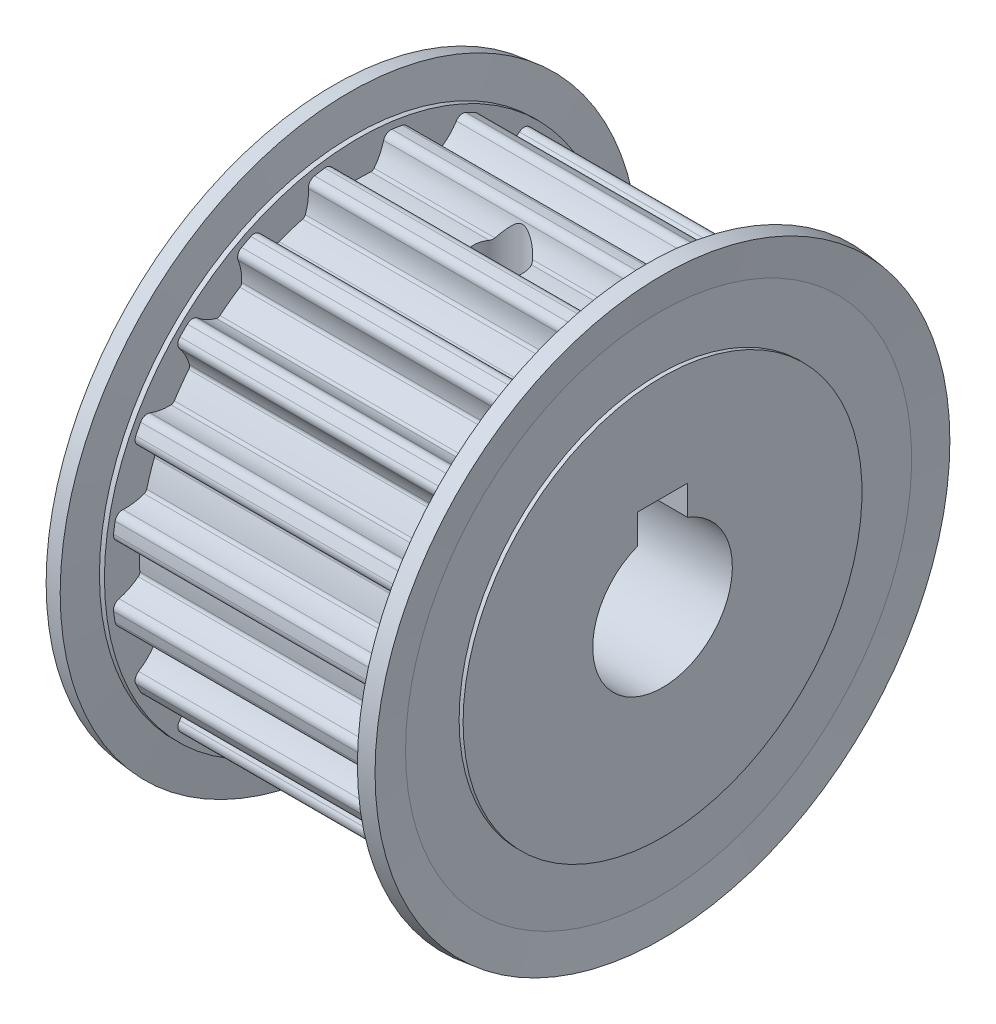
SolidWorks part; units mm, degrees
ref_plane "前视基准面" through (0, 0, 0) normal (0, 0, 1) x (1, 0, 0)
ref_plane "上视基准面" through (0, 0, 0) normal (0, 1, 0) x (1, 0, 0)
ref_plane "右视基准面" through (0, 0, 0) normal (1, 0, 0) x (0, 0, -1)
sketch "草图1" plane through (0, 0, 0) normal (0, 0, 1) x (1, 0, 0)
  line L0 (0, 20) -> (0, 7)
  line L1 (0, 7) -> (48, 7)
  line L2 (48, 7) -> (48, 10.5)
  line L3 (48, 10.5) -> (33, 10.5)
  line L4 (33, 10.5) -> (33, 20)
  line L5 (33, 20) -> (32.6, 20)
  line L6 (32.6, 20) -> (32.6, 25.3748)
  line L7 (32.6, 25.3748) -> (32.9899, 28.8201)
  line L8 (32.9899, 28.8201) -> (31.4, 29)
  line L9 (31.4, 29) -> (31, 25.465)
  line L10 (31, 25.465) -> (30.5, 25.465)
  line L11 (30.5, 25.465) -> (30.5, 24.78)
  line L12 (30.5, 24.78) -> (2.5, 24.78)
  line L13 (2.5, 24.78) -> (2.5, 25.465)
  line L14 (2.5, 25.465) -> (2, 25.465)
  line L15 (2, 25.465) -> (1.6, 29)
  line L16 (1.6, 29) -> (0.0101, 28.8201)
  line L17 (0.0101, 28.8201) -> (0.4, 25.3748)
  line L18 (0.4, 25.3748) -> (0.4, 20)
  line L19 (0.4, 20) -> (0, 20)
  line L20 (48, 0) -> (0, 0) construction
  dimension "D1" = 7
  dimension "D2" = 9.5
revolve "旋转1" add sketch "草图1" angle 360 about L20 reverse direction yes
sketch "草图2" plane through (0, 0, 0) normal (0, 0, 1) x (1, 0, 0)
  line L0 (33, 0) -> (33, 29)
  line L1 (33, 29) -> (66, 29)
  line L2 (66, 29) -> (66, 0)
  line L3 (66, 0) -> (33, 0)
  line L4 (66, 0) -> (33, 0) construction
revolve "切除-旋转1" cut sketch "草图2" angle 360 about L4 reverse direction yes
ref_plane "基准面4" through (2.5, 0, 0) normal (1, 0, 0) x (0, 0, -1)
sketch "草图3" plane through (2.5, 0, 0) normal (1, 0, 0) x (0, 0, -1)
  line L0 (3.3567, 24.5516) -> (3.3567, 33.04)
  line L1 (3.3567, 33.04) -> (-3.3567, 33.04)
  line L2 (-3.3567, 33.04) -> (-3.3567, 24.5516)
  arc A0 (-3.3567, 24.5516) -> (-2.5292, 23.9974) centre (-3.2551, 23.8085) cw
  arc A1 (-2.5292, 23.9974) -> (-1.5758, 22.0681) centre (2.6, 25.3319) ccw
  arc A2 (-1.5758, 22.0681) -> (-1.2381, 21.9151) centre (-1.2607, 22.3144) ccw
  arc A3 (-1.2381, 21.9151) -> (1.2381, 21.9151) centre (0, 0) cw
  arc A4 (1.2381, 21.9151) -> (1.5758, 22.0681) centre (1.2607, 22.3144) ccw
  arc A5 (1.5758, 22.0681) -> (2.5292, 23.9974) centre (-2.6, 25.3319) ccw
  arc A6 (2.5292, 23.9974) -> (3.3567, 24.5516) centre (3.2551, 23.8085) cw
extrude "切除-拉伸1" cut sketch "草图3" along normal blind 28
sketch "草图5" plane through (2.5, 0, 0) normal (1, 0, 0) x (0, 0, -1)
  line L0 (-4.3945, 24.3872) -> (-7.0176, 32.4602)
  line L1 (-7.0176, 32.4602) -> (-13.4023, 30.3856)
  line L2 (-13.4023, 30.3856) -> (-10.7792, 22.3127)
  arc A0 (-10.7792, 22.3127) -> (-9.821, 22.0413) centre (-10.453, 21.6374) cw
  arc A1 (-9.821, 22.0413) -> (-8.3181, 20.501) centre (-5.3552, 24.8955) ccw
  arc A2 (-8.3181, 20.501) -> (-7.9496, 20.4599) centre (-8.0945, 20.8327) ccw
  arc A3 (-7.9496, 20.4599) -> (-5.5946, 21.225) centre (0, 0) cw
  arc A4 (-5.5946, 21.225) -> (-5.3207, 21.475) centre (-5.6966, 21.6118) ccw
  arc A5 (-5.3207, 21.475) -> (-5.0102, 23.6044) centre (-10.3007, 23.2886) ccw
  arc A6 (-5.0102, 23.6044) -> (-4.3945, 24.3872) centre (-4.2615, 23.6491) cw
sketch "草图6" plane through (2.5, 0, 0) normal (1, 0, 0) x (0, 0, -1)
  line L0 (-11.7155, 21.8357) -> (-16.7048, 28.7029)
  line L1 (-16.7048, 28.7029) -> (-22.136, 24.7569)
  line L2 (-22.136, 24.7569) -> (-17.1467, 17.8897)
  arc A0 (-17.1467, 17.8897) -> (-16.1515, 17.9276) centre (-16.6277, 17.3482) cw
  arc A1 (-16.1515, 17.9276) -> (-14.2462, 16.9272) centre (-12.7863, 22.0222) ccw
  arc A2 (-14.2462, 16.9272) -> (-13.883, 17.0019) centre (-14.136, 17.3117) ccw
  arc A3 (-13.883, 17.0019) -> (-11.8797, 18.4574) centre (0, 0) cw
  arc A4 (-11.8797, 18.4574) -> (-11.6964, 18.7797) centre (-12.0962, 18.7937) ccw
  arc A5 (-11.6964, 18.7797) -> (-12.0591, 20.9009) centre (-16.9932, 18.9657) ccw
  arc A6 (-12.0591, 20.9009) -> (-11.7155, 21.8357) centre (-11.3609, 21.1748) cw
sketch "草图7" plane through (2.5, 0, 0) normal (1, 0, 0) x (0, 0, -1)
  line L0 (-17.8897, 17.1467) -> (-24.7569, 22.136)
  line L1 (-24.7569, 22.136) -> (-28.7029, 16.7048)
  line L2 (-28.7029, 16.7048) -> (-21.8357, 11.7155)
  arc A0 (-21.8357, 11.7155) -> (-20.9009, 12.0591) centre (-21.1748, 11.3609) cw
  arc A1 (-20.9009, 12.0591) -> (-18.7797, 11.6964) centre (-18.9657, 16.9932) ccw
  arc A2 (-18.7797, 11.6964) -> (-18.4574, 11.8797) centre (-18.7937, 12.0962) ccw
  arc A3 (-18.4574, 11.8797) -> (-17.0019, 13.883) centre (0, 0) cw
  arc A4 (-17.0019, 13.883) -> (-16.9272, 14.2462) centre (-17.3117, 14.136) ccw
  arc A5 (-16.9272, 14.2462) -> (-17.9276, 16.1515) centre (-22.0222, 12.7863) ccw
  arc A6 (-17.9276, 16.1515) -> (-17.8897, 17.1467) centre (-17.3482, 16.6277) cw
sketch "草图8" plane through (2.5, 0, 0) normal (1, 0, 0) x (0, 0, -1)
  line L0 (-22.3127, 10.7792) -> (-30.3856, 13.4023)
  line L1 (-30.3856, 13.4023) -> (-32.4602, 7.0176)
  line L2 (-32.4602, 7.0176) -> (-24.3872, 4.3945)
  arc A0 (-24.3872, 4.3945) -> (-23.6044, 5.0102) centre (-23.6491, 4.2615) cw
  arc A1 (-23.6044, 5.0102) -> (-21.475, 5.3207) centre (-23.2886, 10.3007) ccw
  arc A2 (-21.475, 5.3207) -> (-21.225, 5.5946) centre (-21.6118, 5.6966) ccw
  arc A3 (-21.225, 5.5946) -> (-20.4599, 7.9496) centre (0, 0) cw
  arc A4 (-20.4599, 7.9496) -> (-20.501, 8.3181) centre (-20.8327, 8.0945) ccw
  arc A5 (-20.501, 8.3181) -> (-22.0413, 9.821) centre (-24.8955, 5.3552) ccw
  arc A6 (-22.0413, 9.821) -> (-22.3127, 10.7792) centre (-21.6374, 10.453) cw
sketch "草图9" plane through (2.5, 0, 0) normal (1, 0, 0) x (0, 0, -1)
  line L0 (-24.5516, 3.3567) -> (-33.04, 3.3567)
  line L1 (-33.04, 3.3567) -> (-33.04, -3.3567)
  line L2 (-33.04, -3.3567) -> (-24.5516, -3.3567)
  arc A0 (-24.5516, -3.3567) -> (-23.9974, -2.5292) centre (-23.8085, -3.2551) cw
  arc A1 (-23.9974, -2.5292) -> (-22.0681, -1.5758) centre (-25.3319, 2.6) ccw
  arc A2 (-22.0681, -1.5758) -> (-21.9151, -1.2381) centre (-22.3144, -1.2607) ccw
  arc A3 (-21.9151, -1.2381) -> (-21.9151, 1.2381) centre (0, 0) cw
  arc A4 (-21.9151, 1.2381) -> (-22.0681, 1.5758) centre (-22.3144, 1.2607) ccw
  arc A5 (-22.0681, 1.5758) -> (-23.9974, 2.5292) centre (-25.3319, -2.6) ccw
  arc A6 (-23.9974, 2.5292) -> (-24.5516, 3.3567) centre (-23.8085, 3.2551) cw
sketch "草图10" plane through (2.5, 0, 0) normal (1, 0, 0) x (0, 0, -1)
  line L0 (-24.3872, -4.3945) -> (-32.4602, -7.0176)
  line L1 (-32.4602, -7.0176) -> (-30.3856, -13.4023)
  line L2 (-30.3856, -13.4023) -> (-22.3127, -10.7792)
  arc A0 (-22.3127, -10.7792) -> (-22.0413, -9.821) centre (-21.6374, -10.453) cw
  arc A1 (-22.0413, -9.821) -> (-20.501, -8.3181) centre (-24.8955, -5.3552) ccw
  arc A2 (-20.501, -8.3181) -> (-20.4599, -7.9496) centre (-20.8327, -8.0945) ccw
  arc A3 (-20.4599, -7.9496) -> (-21.225, -5.5946) centre (0, 0) cw
  arc A4 (-21.225, -5.5946) -> (-21.475, -5.3207) centre (-21.6118, -5.6966) ccw
  arc A5 (-21.475, -5.3207) -> (-23.6044, -5.0102) centre (-23.2886, -10.3007) ccw
  arc A6 (-23.6044, -5.0102) -> (-24.3872, -4.3945) centre (-23.6491, -4.2615) cw
sketch "草图11" plane through (2.5, 0, 0) normal (1, 0, 0) x (0, 0, -1)
  line L0 (-21.8357, -11.7155) -> (-28.7029, -16.7048)
  line L1 (-28.7029, -16.7048) -> (-24.7569, -22.136)
  line L2 (-24.7569, -22.136) -> (-17.8897, -17.1467)
  arc A0 (-17.8897, -17.1467) -> (-17.9276, -16.1515) centre (-17.3482, -16.6277) cw
  arc A1 (-17.9276, -16.1515) -> (-16.9272, -14.2462) centre (-22.0222, -12.7863) ccw
  arc A2 (-16.9272, -14.2462) -> (-17.0019, -13.883) centre (-17.3117, -14.136) ccw
  arc A3 (-17.0019, -13.883) -> (-18.4574, -11.8797) centre (0, 0) cw
  arc A4 (-18.4574, -11.8797) -> (-18.7797, -11.6964) centre (-18.7937, -12.0962) ccw
  arc A5 (-18.7797, -11.6964) -> (-20.9009, -12.0591) centre (-18.9657, -16.9932) ccw
  arc A6 (-20.9009, -12.0591) -> (-21.8357, -11.7155) centre (-21.1748, -11.3609) cw
sketch "草图12" plane through (2.5, 0, 0) normal (1, 0, 0) x (0, 0, -1)
  line L0 (-17.1467, -17.8897) -> (-22.136, -24.7569)
  line L1 (-22.136, -24.7569) -> (-16.7048, -28.7029)
  line L2 (-16.7048, -28.7029) -> (-11.7155, -21.8357)
  arc A0 (-11.7155, -21.8357) -> (-12.0591, -20.9009) centre (-11.3609, -21.1748) cw
  arc A1 (-12.0591, -20.9009) -> (-11.6964, -18.7797) centre (-16.9932, -18.9657) ccw
  arc A2 (-11.6964, -18.7797) -> (-11.8797, -18.4574) centre (-12.0962, -18.7937) ccw
  arc A3 (-11.8797, -18.4574) -> (-13.883, -17.0019) centre (0, 0) cw
  arc A4 (-13.883, -17.0019) -> (-14.2462, -16.9272) centre (-14.136, -17.3117) ccw
  arc A5 (-14.2462, -16.9272) -> (-16.1515, -17.9276) centre (-12.7863, -22.0222) ccw
  arc A6 (-16.1515, -17.9276) -> (-17.1467, -17.8897) centre (-16.6277, -17.3482) cw
sketch "草图13" plane through (2.5, 0, 0) normal (1, 0, 0) x (0, 0, -1)
  line L0 (-10.7792, -22.3127) -> (-13.4023, -30.3856)
  line L1 (-13.4023, -30.3856) -> (-7.0176, -32.4602)
  line L2 (-7.0176, -32.4602) -> (-4.3945, -24.3872)
  arc A0 (-4.3945, -24.3872) -> (-5.0102, -23.6044) centre (-4.2615, -23.6491) cw
  arc A1 (-5.0102, -23.6044) -> (-5.3207, -21.475) centre (-10.3007, -23.2886) ccw
  arc A2 (-5.3207, -21.475) -> (-5.5946, -21.225) centre (-5.6966, -21.6118) ccw
  arc A3 (-5.5946, -21.225) -> (-7.9496, -20.4599) centre (0, 0) cw
  arc A4 (-7.9496, -20.4599) -> (-8.3181, -20.501) centre (-8.0945, -20.8327) ccw
  arc A5 (-8.3181, -20.501) -> (-9.821, -22.0413) centre (-5.3552, -24.8955) ccw
  arc A6 (-9.821, -22.0413) -> (-10.7792, -22.3127) centre (-10.453, -21.6374) cw
sketch "草图14" plane through (2.5, 0, 0) normal (1, 0, 0) x (0, 0, -1)
  line L0 (-3.3567, -24.5516) -> (-3.3567, -33.04)
  line L1 (-3.3567, -33.04) -> (3.3567, -33.04)
  line L2 (3.3567, -33.04) -> (3.3567, -24.5516)
  arc A0 (3.3567, -24.5516) -> (2.5292, -23.9974) centre (3.2551, -23.8085) cw
  arc A1 (2.5292, -23.9974) -> (1.5758, -22.0681) centre (-2.6, -25.3319) ccw
  arc A2 (1.5758, -22.0681) -> (1.2381, -21.9151) centre (1.2607, -22.3144) ccw
  arc A3 (1.2381, -21.9151) -> (-1.2381, -21.9151) centre (0, 0) cw
  arc A4 (-1.2381, -21.9151) -> (-1.5758, -22.0681) centre (-1.2607, -22.3144) ccw
  arc A5 (-1.5758, -22.0681) -> (-2.5292, -23.9974) centre (2.6, -25.3319) ccw
  arc A6 (-2.5292, -23.9974) -> (-3.3567, -24.5516) centre (-3.2551, -23.8085) cw
sketch "草图15" plane through (2.5, 0, 0) normal (1, 0, 0) x (0, 0, -1)
  line L0 (4.3945, -24.3872) -> (7.0176, -32.4602)
  line L1 (7.0176, -32.4602) -> (13.4023, -30.3856)
  line L2 (13.4023, -30.3856) -> (10.7792, -22.3127)
  arc A0 (10.7792, -22.3127) -> (9.821, -22.0413) centre (10.453, -21.6374) cw
  arc A1 (9.821, -22.0413) -> (8.3181, -20.501) centre (5.3552, -24.8955) ccw
  arc A2 (8.3181, -20.501) -> (7.9496, -20.4599) centre (8.0945, -20.8327) ccw
  arc A3 (7.9496, -20.4599) -> (5.5946, -21.225) centre (0, 0) cw
  arc A4 (5.5946, -21.225) -> (5.3207, -21.475) centre (5.6966, -21.6118) ccw
  arc A5 (5.3207, -21.475) -> (5.0102, -23.6044) centre (10.3007, -23.2886) ccw
  arc A6 (5.0102, -23.6044) -> (4.3945, -24.3872) centre (4.2615, -23.6491) cw
sketch "草图16" plane through (2.5, 0, 0) normal (1, 0, 0) x (0, 0, -1)
  line L0 (11.7155, -21.8357) -> (16.7048, -28.7029)
  line L1 (16.7048, -28.7029) -> (22.136, -24.7569)
  line L2 (22.136, -24.7569) -> (17.1467, -17.8897)
  arc A0 (17.1467, -17.8897) -> (16.1515, -17.9276) centre (16.6277, -17.3482) cw
  arc A1 (16.1515, -17.9276) -> (14.2462, -16.9272) centre (12.7863, -22.0222) ccw
  arc A2 (14.2462, -16.9272) -> (13.883, -17.0019) centre (14.136, -17.3117) ccw
  arc A3 (13.883, -17.0019) -> (11.8797, -18.4574) centre (0, 0) cw
  arc A4 (11.8797, -18.4574) -> (11.6964, -18.7797) centre (12.0962, -18.7937) ccw
  arc A5 (11.6964, -18.7797) -> (12.0591, -20.9009) centre (16.9932, -18.9657) ccw
  arc A6 (12.0591, -20.9009) -> (11.7155, -21.8357) centre (11.3609, -21.1748) cw
sketch "草图17" plane through (2.5, 0, 0) normal (1, 0, 0) x (0, 0, -1)
  line L0 (17.8897, -17.1467) -> (24.7569, -22.136)
  line L1 (24.7569, -22.136) -> (28.7029, -16.7048)
  line L2 (28.7029, -16.7048) -> (21.8357, -11.7155)
  arc A0 (21.8357, -11.7155) -> (20.9009, -12.0591) centre (21.1748, -11.3609) cw
  arc A1 (20.9009, -12.0591) -> (18.7797, -11.6964) centre (18.9657, -16.9932) ccw
  arc A2 (18.7797, -11.6964) -> (18.4574, -11.8797) centre (18.7937, -12.0962) ccw
  arc A3 (18.4574, -11.8797) -> (17.0019, -13.883) centre (0, 0) cw
  arc A4 (17.0019, -13.883) -> (16.9272, -14.2462) centre (17.3117, -14.136) ccw
  arc A5 (16.9272, -14.2462) -> (17.9276, -16.1515) centre (22.0222, -12.7863) ccw
  arc A6 (17.9276, -16.1515) -> (17.8897, -17.1467) centre (17.3482, -16.6277) cw
sketch "草图18" plane through (2.5, 0, 0) normal (1, 0, 0) x (0, 0, -1)
  line L0 (22.3127, -10.7792) -> (30.3856, -13.4023)
  line L1 (30.3856, -13.4023) -> (32.4602, -7.0176)
  line L2 (32.4602, -7.0176) -> (24.3872, -4.3945)
  arc A0 (24.3872, -4.3945) -> (23.6044, -5.0102) centre (23.6491, -4.2615) cw
  arc A1 (23.6044, -5.0102) -> (21.475, -5.3207) centre (23.2886, -10.3007) ccw
  arc A2 (21.475, -5.3207) -> (21.225, -5.5946) centre (21.6118, -5.6966) ccw
  arc A3 (21.225, -5.5946) -> (20.4599, -7.9496) centre (0, 0) cw
  arc A4 (20.4599, -7.9496) -> (20.501, -8.3181) centre (20.8327, -8.0945) ccw
  arc A5 (20.501, -8.3181) -> (22.0413, -9.821) centre (24.8955, -5.3552) ccw
  arc A6 (22.0413, -9.821) -> (22.3127, -10.7792) centre (21.6374, -10.453) cw
sketch "草图19" plane through (2.5, 0, 0) normal (1, 0, 0) x (0, 0, -1)
  line L0 (24.5516, -3.3567) -> (33.04, -3.3567)
  line L1 (33.04, -3.3567) -> (33.04, 3.3567)
  line L2 (33.04, 3.3567) -> (24.5516, 3.3567)
  arc A0 (24.5516, 3.3567) -> (23.9974, 2.5292) centre (23.8085, 3.2551) cw
  arc A1 (23.9974, 2.5292) -> (22.0681, 1.5758) centre (25.3319, -2.6) ccw
  arc A2 (22.0681, 1.5758) -> (21.9151, 1.2381) centre (22.3144, 1.2607) ccw
  arc A3 (21.9151, 1.2381) -> (21.9151, -1.2381) centre (0, 0) cw
  arc A4 (21.9151, -1.2381) -> (22.0681, -1.5758) centre (22.3144, -1.2607) ccw
  arc A5 (22.0681, -1.5758) -> (23.9974, -2.5292) centre (25.3319, 2.6) ccw
  arc A6 (23.9974, -2.5292) -> (24.5516, -3.3567) centre (23.8085, -3.2551) cw
sketch "草图20" plane through (2.5, 0, 0) normal (1, 0, 0) x (0, 0, -1)
  line L0 (24.3872, 4.3945) -> (32.4602, 7.0176)
  line L1 (32.4602, 7.0176) -> (30.3856, 13.4023)
  line L2 (30.3856, 13.4023) -> (22.3127, 10.7792)
  arc A0 (22.3127, 10.7792) -> (22.0413, 9.821) centre (21.6374, 10.453) cw
  arc A1 (22.0413, 9.821) -> (20.501, 8.3181) centre (24.8955, 5.3552) ccw
  arc A2 (20.501, 8.3181) -> (20.4599, 7.9496) centre (20.8327, 8.0945) ccw
  arc A3 (20.4599, 7.9496) -> (21.225, 5.5946) centre (0, 0) cw
  arc A4 (21.225, 5.5946) -> (21.475, 5.3207) centre (21.6118, 5.6966) ccw
  arc A5 (21.475, 5.3207) -> (23.6044, 5.0102) centre (23.2886, 10.3007) ccw
  arc A6 (23.6044, 5.0102) -> (24.3872, 4.3945) centre (23.6491, 4.2615) cw
sketch "草图21" plane through (2.5, 0, 0) normal (1, 0, 0) x (0, 0, -1)
  line L0 (21.8357, 11.7155) -> (28.7029, 16.7048)
  line L1 (28.7029, 16.7048) -> (24.7569, 22.136)
  line L2 (24.7569, 22.136) -> (17.8897, 17.1467)
  arc A0 (17.8897, 17.1467) -> (17.9276, 16.1515) centre (17.3482, 16.6277) cw
  arc A1 (17.9276, 16.1515) -> (16.9272, 14.2462) centre (22.0222, 12.7863) ccw
  arc A2 (16.9272, 14.2462) -> (17.0019, 13.883) centre (17.3117, 14.136) ccw
  arc A3 (17.0019, 13.883) -> (18.4574, 11.8797) centre (0, 0) cw
  arc A4 (18.4574, 11.8797) -> (18.7797, 11.6964) centre (18.7937, 12.0962) ccw
  arc A5 (18.7797, 11.6964) -> (20.9009, 12.0591) centre (18.9657, 16.9932) ccw
  arc A6 (20.9009, 12.0591) -> (21.8357, 11.7155) centre (21.1748, 11.3609) cw
sketch "草图22" plane through (2.5, 0, 0) normal (1, 0, 0) x (0, 0, -1)
  line L0 (17.1467, 17.8897) -> (22.136, 24.7569)
  line L1 (22.136, 24.7569) -> (16.7048, 28.7029)
  line L2 (16.7048, 28.7029) -> (11.7155, 21.8357)
  arc A0 (11.7155, 21.8357) -> (12.0591, 20.9009) centre (11.3609, 21.1748) cw
  arc A1 (12.0591, 20.9009) -> (11.6964, 18.7797) centre (16.9932, 18.9657) ccw
  arc A2 (11.6964, 18.7797) -> (11.8797, 18.4574) centre (12.0962, 18.7937) ccw
  arc A3 (11.8797, 18.4574) -> (13.883, 17.0019) centre (0, 0) cw
  arc A4 (13.883, 17.0019) -> (14.2462, 16.9272) centre (14.136, 17.3117) ccw
  arc A5 (14.2462, 16.9272) -> (16.1515, 17.9276) centre (12.7863, 22.0222) ccw
  arc A6 (16.1515, 17.9276) -> (17.1467, 17.8897) centre (16.6277, 17.3482) cw
sketch "草图23" plane through (2.5, 0, 0) normal (1, 0, 0) x (0, 0, -1)
  line L0 (10.7792, 22.3127) -> (13.4023, 30.3856)
  line L1 (13.4023, 30.3856) -> (7.0176, 32.4602)
  line L2 (7.0176, 32.4602) -> (4.3945, 24.3872)
  arc A0 (4.3945, 24.3872) -> (5.0102, 23.6044) centre (4.2615, 23.6491) cw
  arc A1 (5.0102, 23.6044) -> (5.3207, 21.475) centre (10.3007, 23.2886) ccw
  arc A2 (5.3207, 21.475) -> (5.5946, 21.225) centre (5.6966, 21.6118) ccw
  arc A3 (5.5946, 21.225) -> (7.9496, 20.4599) centre (0, 0) cw
  arc A4 (7.9496, 20.4599) -> (8.3181, 20.501) centre (8.0945, 20.8327) ccw
  arc A5 (8.3181, 20.501) -> (9.821, 22.0413) centre (5.3552, 24.8955) ccw
  arc A6 (9.821, 22.0413) -> (10.7792, 22.3127) centre (10.453, 21.6374) cw
extrude "切除-拉伸2" cut sketch "草图5" along normal blind 28
extrude "切除-拉伸3" cut sketch "草图6" along normal blind 28
extrude "切除-拉伸4" cut sketch "草图7" along normal blind 28
extrude "切除-拉伸5" cut sketch "草图8" along normal blind 28
extrude "切除-拉伸6" cut sketch "草图9" along normal blind 28
extrude "切除-拉伸7" cut sketch "草图10" along normal blind 28
extrude "切除-拉伸8" cut sketch "草图11" along normal blind 28
extrude "切除-拉伸9" cut sketch "草图12" along normal blind 28
extrude "切除-拉伸10" cut sketch "草图13" along normal blind 28
extrude "切除-拉伸11" cut sketch "草图14" along normal blind 28
extrude "切除-拉伸12" cut sketch "草图15" along normal blind 28
extrude "切除-拉伸13" cut sketch "草图16" along normal blind 28
extrude "切除-拉伸14" cut sketch "草图17" along normal blind 28
extrude "切除-拉伸15" cut sketch "草图18" along normal blind 28
extrude "切除-拉伸16" cut sketch "草图19" along normal blind 28
extrude "切除-拉伸17" cut sketch "草图20" along normal blind 28
extrude "切除-拉伸18" cut sketch "草图21" along normal blind 28
extrude "切除-拉伸19" cut sketch "草图22" along normal blind 28
extrude "切除-拉伸20" cut sketch "草图23" along normal blind 28
ref_plane "基准面5" through (16.5, 0, 0) normal (1, 0, 0) x (0, 0, -1)
sketch "草图24" plane through (16.5, 0, 0) normal (1, 0, 0) x (0, 0, -1)
  line L0 (0, 24.78) -> (2.4585, 24.78)
  line L1 (2.4585, 24.78) -> (2.4585, 0)
  line L2 (2.4585, 0) -> (0, 0)
  line L3 (0, 0) -> (0, 24.78)
  line L4 (0, 12.3) -> (0, 24.78) construction
revolve "切除-旋转2" cut sketch "草图24" angle 360 about L4 reverse direction yes
cosmetic thread "装饰螺纹线1" parameters "D1"=26.0658, "D2"=6
sketch "草图25" plane through (16.5, 0, 0) normal (1, 0, 0) x (0, 0, -1)
  line L0 (21.4601, -12.39) -> (20.2309, -14.5191)
  line L1 (20.2309, -14.5191) -> (-1.2292, -2.1291)
  line L2 (-1.2292, -2.1291) -> (0, 0)
  line L3 (0, 0) -> (21.4601, -12.39)
  line L4 (7.7942, -4.5) -> (21.4601, -12.39) construction
revolve "切除-旋转3" cut sketch "草图25" angle 360 about L4 reverse direction yes
sketch "草图26" plane through (0, 0, 0) normal (1, 0, 0) x (0, 0, -1)
  line L1 (-2.5, 9.5) -> (2.5, 9.5)
  line L2 (-2.5, 9.5) -> (-2.5, -0.5)
  line L3 (-2.5, -0.5) -> (2.5, -0.5)
  line L4 (2.5, 9.5) -> (2.5, -0.5)
  line L5 (-2.5, 9.5) -> (2.5, -0.5) construction
  line L6 (-2.5, -0.5) -> (2.5, 9.5) construction
  point P0 (0, 4.5)
  dimension "D1" = 5
  dimension "D2" = 0
  dimension "D3" = 9.5
  dimension "D4" = 10
extrude "切除-拉伸21" cut sketch "草图26" along normal blind 48
ref_plane "基准面6" through (0, 0, 0) normal (0, 0.866, 0.5) x (1, 0, 0)
ref_plane "基准面7" through (0, 0, 0) normal (0, -0.5, 0.866) x (1, 0, 0)
ref_plane "基准面8" through (33, 0, 0) normal (1, 0, 0) x (0, 0, -1)
ref_plane "基准面9" through (0, 0, 0) normal (0, 0, -1) x (-1, 0, 0)
ref_plane "基准面10" through (0, 24.78, 0) normal (0, 1, 0) x (1, 0, 0)
ref_plane "基准面11" through (0, 0, 0) normal (0, -0.5, -0.866) x (-1, 0, 0)
ref_plane "基准面12" through (0, -12.39, -21.4601) normal (0, -0.5, -0.866) x (-1, 0, 0)
ref_plane "to_s1 XY" through (0, 24.78, 0) normal (0, 1, 0) x (1, 0, 0)
ref_plane "to_s1 XZ" through (0, 0, 0) normal (0, 0, 1) x (1, 0, 0)
ref_plane "to_s1 YZ" through (16.5, 0, 0) normal (1, 0, 0) x (0, 0, -1)
ref_axis "to_s1 X" through (-80.9, 24.78, 0) along (1, 0, 0)
ref_axis "to_s1 Y" through (16.5, 24.78, 50) along (0, 0, -1)
ref_axis "to_s1 Z" through (16.5, 50, 0) along (0, -1, 0)
sketch3d "to_s1"
  point P0 (16.5, 24.78, 0)
ref_plane "to_s2 XY" through (0, -12.39, -21.4601) normal (0, -0.5, -0.866) x (-1, 0, 0)
ref_plane "to_s2 XZ" through (0, 0, 0) normal (0, 0.866, -0.5) x (1, 0, 0)
ref_plane "to_s2 YZ" through (16.5, 0, 0) normal (1, 0, 0) x (0, 0, -1)
ref_axis "to_s2 X" through (-80.9, -12.39, -21.4601) along (1, 0, 0)
ref_axis "to_s2 Y" through (16.5, 30.9113, -46.4601) along (0, -0.866, 0.5)
ref_axis "to_s2 Z" through (16.5, -46.7076, -80.9) along (0, 0.5, 0.866)
sketch3d "to_s2"
  point P0 (16.5, -12.39, -21.4601)
